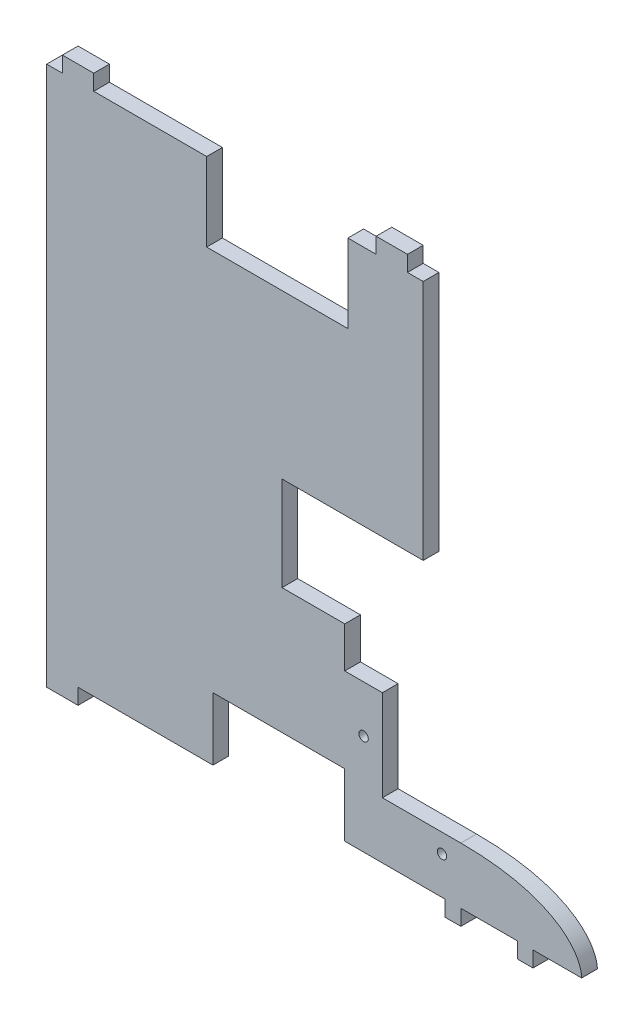
SolidWorks part; units mm, degrees
ref_plane "Plan de face" through (0, 0, 0) normal (0, 0, 1) x (1, 0, 0)
ref_plane "Plan de dessus" through (0, 0, 0) normal (0, 1, 0) x (1, 0, 0)
ref_plane "Plan de droite" through (0, 0, 0) normal (1, 0, 0) x (0, 0, -1)
sketch "Esquisse1" plane through (0, 0, 0) normal (0, 0, 1) x (1, 0, 0)
  line L1 (0, 0) -> (32, 0)
  line L2 (0, 0) -> (0, 47)
  line L3 (0, 47) -> (12, 47)
  line L4 (37, 0) -> (37, 18)
  line L6 (12, 47) -> (12, 18)
  line L7 (12, 18) -> (37, 18)
  line L8 (37, 0) -> (37, -5)
  line L9 (37, -5) -> (32, -5)
  line L10 (32, 0) -> (32, -5)
  circle A0 centre (6, 32) radius 1.5
  circle A1 centre (31, 12) radius 1.5
  dimension "D3" = 20
  dimension "D4" = 3
  dimension "D1" = 6
  dimension "D2" = 12
  dimension "D5" = 15
  dimension "D6" = 6
  dimension "D7" = 25
  dimension "D8" = 6
  dimension "D9" = 6
  dimension "D10" = 5
  dimension "D11" = 5
extrude "Boss.-Extru.1" add sketch "Esquisse1" along normal blind 5
sketch "Esquisse2" plane through (0, 0, 0) normal (0, 0, -1) x (-1, 0, 0)
  line L0 (-37, 18) -> (-12, 18) construction
  line L1 (-37, 0) -> (-55, 0)
  line L2 (-37, 0) -> (-37, 18)
  line L3 (-60, 0) -> (-75.5, 0)
  line L4 (42, 0) -> (85, 0)
  line L5 (0, 20) -> (0, 60)
  line L6 (0, 60) -> (20, 60)
  line L7 (-10, 167) -> (-1, 167)
  line L8 (0, 0) -> (-32, 0) construction
  line L9 (20, 60) -> (20, 90)
  line L10 (44, 167) -> (80, 167)
  line L11 (95, -5) -> (95, 167)
  line L12 (95, -5) -> (85, -5)
  line L13 (85, 0) -> (85, -5)
  line L14 (90, 167) -> (95, 167)
  line L15 (-60, 0) -> (-60, -5)
  line L16 (-60, -5) -> (-55, -5)
  line L17 (-55, 0) -> (-55, -5)
  line L18 (0, 20) -> (42, 20)
  line L19 (90, 167) -> (90, 172)
  line L20 (90, 172) -> (80, 172)
  line L21 (80, 167) -> (80, 172)
  line L22 (0, 47) -> (0, 0) construction
  line L23 (-20, 167) -> (-20, 172)
  line L24 (-20, 172) -> (-10, 172)
  line L25 (-10, 167) -> (-10, 172)
  line L26 (0, 0) -> (-32, 0) construction
  line L27 (42, 20) -> (42, 0)
  line L29 (-37, -5) -> (-37, 18) construction
  line L30 (-1, 167) -> (-1, 142)
  line L31 (20, 90) -> (-25, 90)
  line L32 (-1, 142) -> (44, 142)
  line L33 (-20, 167) -> (-25, 167)
  line L34 (-25, 90) -> (-25, 167)
  line L35 (44, 167) -> (44, 142)
  spline S0 degree 3 poles (-75.5, 0) (-75.5, 5.9822) (-67.6854, 18) (-37, 18) knots 0 0 0 0 1 1 1 1
  dimension "D1" = 38.5
  dimension "D2" = 20
  dimension "D3" = 167
  dimension "D4" = 95
  dimension "D5" = 5
  dimension "D6" = 30
  dimension "D7" = 5
  dimension "D8" = 10
  dimension "D9" = 10
  dimension "D10" = 10
  dimension "D11" = 140
  dimension "D12" = 5
  dimension "D13" = 42
  dimension "D14" = 20
  dimension "D15" = 40
  dimension "D16" = 45
  dimension "D17" = 5
  dimension "D18" = 5
  dimension "D19" = 25
  dimension "D20" = 45
  dimension "D21" = 24
extrude "Boss.-Extru.2" add sketch "Esquisse2" against normal blind 5
